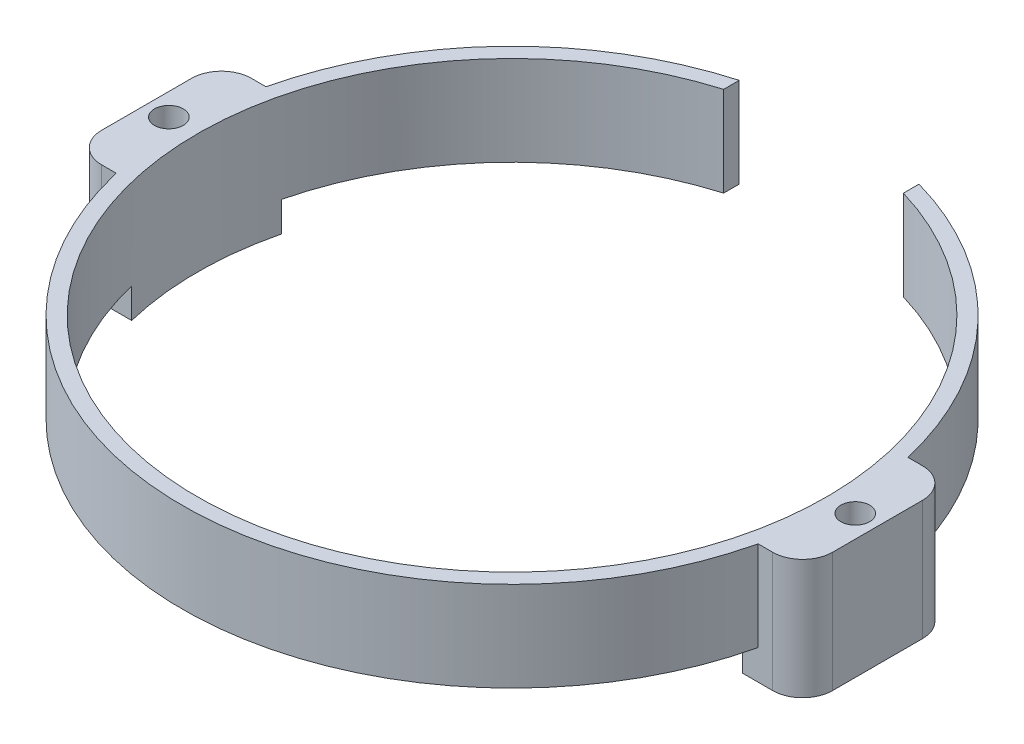
SolidWorks part; units mm, degrees
ref_plane "Front Plane" through (0, 0, 0) normal (0, 0, 1) x (1, 0, 0)
ref_plane "Top Plane" through (0, 0, 0) normal (0, 1, 0) x (1, 0, 0)
ref_plane "Right Plane" through (0, 0, 0) normal (1, 0, 0) x (0, 0, -1)
sketch "Sketch1" plane through (0, 0, 0) normal (0, 1, 0) x (1, 0, 0)
  circle A0 centre (0, 0) radius 52.5
  circle A1 centre (0, 0) radius 55
  dimension "D1" = 110
  dimension "D2" = 105
extrude "Boss-Extrude1" add sketch "Sketch1" along normal blind 10 and the other way blind 5
sketch "Sketch2" plane through (0, 10, 0) normal (0, 1, 0) x (1, 0, 0)
  line L0 (0, 0) -> (-15, 0)
  line L1 (-15, 0) -> (-15, 70)
  line L2 (-15, 70) -> (15, 70)
  line L3 (15, 70) -> (15, 0)
  line L4 (15, 0) -> (0, 0)
  dimension "D1" = 70
  dimension "D2" = 15
  dimension "D3" = 15
extrude "Cut-Extrude2" cut sketch "Sketch2" against normal through all contours L4 L0 L1 L2 L3
sketch "Sketch3" plane through (0, 10, 0) normal (0, 1, 0) x (1, 0, 0)
  circle A0 centre (0, 0) radius 55
sketch "Sketch4" plane through (0, -5, 0) normal (0, -1, 0) x (1, 0, 0)
  circle A0 centre (0, 0) radius 55
sketch "Sketch6" plane through (0, 10, 0) normal (0, 1, 0) x (1, 0, 0)
  line L0 (50.9902, 12.5) -> (60.9902, 12.5)
  line L1 (-60.9902, -12.5) -> (-50.9902, -12.5)
  line L2 (-60.9902, -12.5) -> (-60.9902, 12.5)
  line L3 (-60.9902, 12.5) -> (-50.9902, 12.5)
  line L4 (60.9902, -12.5) -> (60.9902, 12.5)
  line L9 (50.9902, -12.5) -> (60.9902, -12.5)
  arc A0 (-50.9902, 12.5) -> (-50.9902, -12.5) centre (0, 0) ccw
  arc A1 (50.9902, -12.5) -> (50.9902, 12.5) centre (0, 0) ccw
  arc A2 (-15, 50.3115) -> (15, 50.3115) centre (0, 0) ccw construction
  point P0 (0, 0)
  dimension "D1" = 25
  dimension "D2" = 10
  dimension "D3" = 10
extrude "Boss-Extrude4" add sketch "Sketch6" against normal blind 20
sketch "Sketch7" plane through (0, 10, 0) normal (0, 1, 0) x (1, 0, 0)
  circle A0 centre (-57.2755, 0) radius 2.4
  circle A1 centre (57.2755, 0) radius 2.4
  dimension "D1" = 4.8
  dimension "D2" = 4.8
extrude "Cut-Extrude4" cut sketch "Sketch7" against normal through all contours A0 | A1
fillet "Fillet1" radius 5 4 edges at (60.9902, 0, -12.5) (60.9902, 0, 12.5) (-60.9902, 0, 12.5) (-60.9902, 0, -12.5)
sketch "Sketch8" plane through (15, 0, 0) normal (-1, 0, 0) x (0, 0, 1)
  line L1 (-52.915, 10) -> (-50.3115, 10)
  line L2 (-52.915, 10) -> (-52.915, -5)
  line L3 (-52.915, -5) -> (-50.3115, -5)
  line L4 (-50.3115, 10) -> (-50.3115, -5)
extrude "Boss-Extrude5" [suppressed] add sketch "Sketch8" along normal blind 5
sketch "Sketch9" [suppressed] plane through (0, -5, 0) normal (0, -1, 0) x (1, 0, 0)
  line L0 (10, -50.3115) -> (15, -50.3115) construction
  line L1 (10, -52.915) -> (15, -52.915)
  line L2 (10, -52.915) -> (10, -50.3115)
  line L3 (10, -50.3115) -> (15, -50.3115)
  line L4 (15, -52.915) -> (15, -50.3115)
  arc A0 (-50.9902, -12.5) -> (-15, -50.3115) centre (0, 0) ccw construction
extrude "Boss-Extrude6" [suppressed] add sketch "Sketch9" along normal blind 10
sketch "Sketch11" [suppressed] plane through (0, 10, 0) normal (0, 1, 0) x (1, 0, 0)
  line L0 (-78.2995, -7.085) -> (72.495, -7.085)
  line L1 (10, 52.915) -> (15, 52.915) construction
  line L2 (10, 52.915) -> (-7.427, 36.0556)
  line L3 (10, 52.915) -> (15, 52.915)
  line L4 (15, 52.915) -> (15, 50.3115)
  line L5 (15, 50.3115) -> (0.2642, 36.0556)
  line L6 (-44.3286, -7.085) -> (-52.0197, -7.085)
  line L7 (-7.427, 36.0556) -> (0.2642, 36.0556)
  arc A0 (-15, 50.3115) -> (15, 50.3115) centre (0, 0) ccw construction
  arc A1 (53.5607, 12.5) -> (15, 52.915) centre (0, 0) ccw construction
  line M9 (10, 52.915) -> (10, 50.3115)
  line M10 (10, 50.3115) -> (15, 50.3115)
  dimension "D1" = 60
extrude "Boss-Extrude8" [suppressed] add sketch "Sketch11" against normal blind 10 from offset 15 contours L2 L7 L5 M10 M9 offset against normal yes
